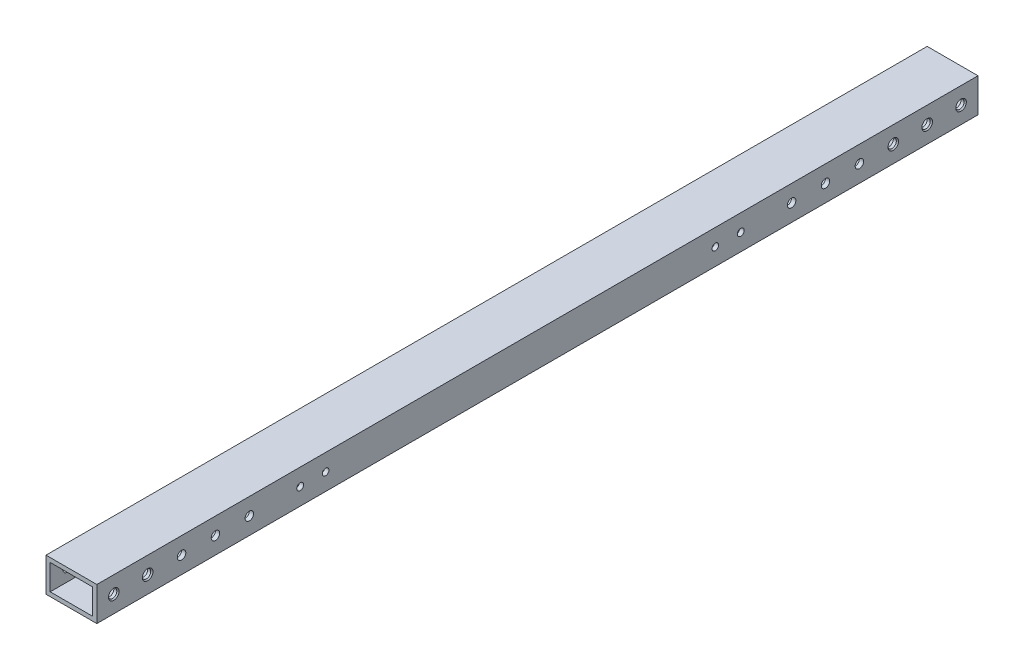
SolidWorks part; units mm, degrees
ref_plane "Front Plane" through (0, 0, 0) normal (0, 0, 1) x (1, 0, 0)
ref_plane "Top Plane" through (0, 0, 0) normal (0, 1, 0) x (1, 0, 0)
ref_plane "Right Plane" through (0, 0, 0) normal (1, 0, 0) x (0, 0, -1)
sketch "Sketch1" plane through (0, 0, 0) normal (0, 0, 1) x (1, 0, 0)
  line L0 (-15.875, 9.525) -> (15.875, 9.525)
  line L2 (-19.05, 12.7) -> (19.05, 12.7)
  line L3 (-19.05, 12.7) -> (-19.05, -12.7)
  line L4 (-19.05, -12.7) -> (19.05, -12.7)
  line L5 (19.05, 12.7) -> (19.05, -12.7)
  line L10 (15.875, 9.525) -> (15.875, -9.525)
  line L11 (-15.875, -9.525) -> (15.875, -9.525)
  line L12 (-15.875, 9.525) -> (-15.875, -9.525)
  point P12 (0, 12.7)
  point P14 (19.05, 0)
  dimension "Wall Thickness" = 3.175
  dimension "Outside Width" = 38.1
  dimension "Outside Height" = 25.4
  dimension "Inside Height" = 19.05
  dimension "Inside Width" = 31.75
sketch "Sketch2" plane through (0, 0, 0) normal (1, 0, 0) x (0, 0, -1)
  line L0 (330.2, 0) -> (-330.2, 0)
  point P4 (0, 0)
  point P7 (-330.2, 0)
  point P10 (330.2, 0)
  dimension "Length" = 660.4
sketch "Sketch3" plane through (0, 0, 0) normal (0, 0, 1) x (1, 0, 0)
  line L21 (19.05, 12.7) -> (-19.05, 12.7)
  line L22 (19.05, -12.7) -> (19.05, 12.7)
  line L23 (-19.05, -12.7) -> (19.05, -12.7)
  line L24 (-19.05, 12.7) -> (-19.05, -12.7)
  line L25 (19.05, 12.7) -> (-19.05, 12.7)
  line L26 (19.05, -12.7) -> (19.05, 12.7)
  line L27 (-19.05, -12.7) -> (19.05, -12.7)
  line L28 (-19.05, 12.7) -> (-19.05, -12.7)
  line L29 (15.875, 9.525) -> (-15.875, 9.525)
  line L30 (15.875, -9.525) -> (15.875, 9.525)
  line L31 (-15.875, -9.525) -> (15.875, -9.525)
  line L32 (-15.875, 9.525) -> (-15.875, -9.525)
  line L33 (15.875, 9.525) -> (-15.875, 9.525)
  line L34 (15.875, -9.525) -> (15.875, 9.525)
  line L35 (-15.875, -9.525) -> (15.875, -9.525)
  line L36 (-15.875, 9.525) -> (-15.875, -9.525)
  dimension "D1" = 0
  dimension "D2" = 0
extrude "Boss-Extrude1" add sketch "Sketch3" along normal up to vertex (330.2 mm away) and the other way up to vertex (330.2 mm away) up to point (0, 0, 330.2) other way up to point (0, 0, -330.2)
sketch "Drawing Reference" plane through (0, 0, 0) normal (1, 0, 0) x (0, 0, -1)
  line L0 (-330.2, 0) -> (330.2, 0) construction
  line L1 (0, -12.7) -> (0, 12.7) construction
  line L2 (-330.2, -12.7) -> (330.2, -12.7) construction
  line L5 (-330.2, 12.7) -> (330.2, 12.7) construction
  point P7 (-302.768, 0)
  point P8 (302.768, 0)
  dimension "D1" = 27.432
sketch "Sketch4" plane through (-19.05, 0, 0) normal (-1, 0, 0) x (0, 0, 1)
  line L0 (-330.2, 0) -> (-317.5, 0)
  line L1 (-330.2, 12.7) -> (-330.2, -12.7) construction
  line L2 (-317.5, 0) -> (-292.1, 0)
  line L3 (-292.1, 0) -> (-266.7, 0)
  line L4 (-266.7, 0) -> (-241.3, 0)
  line L5 (-241.3, 0) -> (-215.9, 0)
  line L6 (-215.9, 0) -> (-190.5, 0)
  line L7 (330.2, 0) -> (317.5, 0)
  line L8 (330.2, 12.7) -> (330.2, -12.7) construction
  line L9 (317.5, 0) -> (292.1, 0)
  line L10 (292.1, 0) -> (266.7, 0)
  line L11 (266.7, 0) -> (241.3, 0)
  line L12 (241.3, 0) -> (215.9, 0)
  line L13 (-190.5, 0) -> (-133.35, 0)
  line L14 (-190.5, 0) -> (-152.4, 0) construction
  line L15 (215.9, 0) -> (158.75, 0)
hole_wizard "1/4 (0.25) Diameter Hole2" positions "Sketch7" profile "Sketch8" hole size "1/4" standard "ANSI Inch" end condition through all
sketch "Sketch7" plane through (-19.05, 0, 0) normal (-1, 0, 0) x (0, 0, 1)
  point P0 (-317.5, 0)
  point P3 (-292.1, 0)
  point P7 (317.5, 0)
  point P11 (-266.7, 0)
  point P14 (292.1, 0)
sketch "Sketch8" plane through (-19.05, 0, -317.5) normal (0, 1, 0) x (0, 0, 1)
  line L0 (0, 0) -> (0, 38.1)
  line L1 (0, 38.1) -> (3.9624, 38.1)
  line L2 (3.175, 37.1942) -> (3.175, 0)
  line L5 (3.175, 0) -> (0, 0)
  line L7 (3.9624, 38.1) -> (3.175, 37.1942)
  line L8 (-3.9624, 38.1) -> (-3.175, 37.1942) construction
  line L11 (0, -6.35) -> (0, 107.95) construction
  dimension "Thru Hole Dia." = 6.35
  dimension "Thru Hole Depth" = 38.1
  dimension "Far C'Sink Dia." = 7.9248
  dimension "Far C'Sink Angle" = 82
hole_wizard "1/4 (0.25) Diameter Hole3" positions "Sketch9" profile "Sketch10" hole size "1/4" standard "ANSI Inch" end condition through all
sketch "Sketch9" plane through (19.05, 0, 0) normal (1, 0, 0) x (0, 0, -1)
  point P0 (-266.7, 0)
  point P3 (-241.3, 0)
  point P6 (-215.9, 0)
  point P9 (241.3, 0)
  point P12 (215.9, 0)
  point P15 (190.5, 0)
sketch "Sketch10" plane through (19.05, 0, 266.7) normal (0, 1, 0) x (0, 0, -1)
  line L0 (0, 0) -> (0, 38.1)
  line L1 (0, 38.1) -> (3.175, 38.1)
  line L2 (3.175, 38.1) -> (3.175, 0)
  line L5 (3.175, 0) -> (0, 0)
  line L11 (0, -6.35) -> (0, 107.95) construction
  dimension "Thru Hole Dia." = 6.35
  dimension "Thru Hole Depth" = 38.1
hole_wizard "13/64 (0.20313) Diameter Hole1" positions "Sketch11" profile "Sketch12" hole size "13/64" standard "ANSI Inch" end condition through all
sketch "Sketch11" plane through (19.05, 0, 0) normal (1, 0, 0) x (0, 0, -1)
  point P0 (152.4, 0)
  point P7 (-177.8, 0)
sketch "Sketch12" plane through (19.05, 0, -152.4) normal (0, 1, 0) x (0, 0, -1)
  line L0 (0, 0) -> (0, 38.1)
  line L1 (0, 38.1) -> (2.5798, 38.1)
  line L2 (2.5798, 38.1) -> (2.5798, 0)
  line L5 (2.5798, 0) -> (0, 0)
  line L11 (0, -6.35) -> (0, 107.95) construction
  dimension "Thru Hole Dia." = 5.1595
  dimension "Thru Hole Depth" = 38.1
hole_wizard "#10 Clearance Hole1" positions "Sketch13" profile "Sketch14" hole size "#10" standard "ANSI Inch" end condition through all
sketch "Sketch13" plane through (-19.05, 0, 0) normal (-1, 0, 0) x (0, 0, 1)
  point P0 (-133.35, 0)
  point P3 (158.75, 0)
sketch "Sketch14" plane through (-19.05, 0, -133.35) normal (0, 1, 0) x (0, 0, 1)
  line L0 (0, 0) -> (0, 38.1)
  line L1 (0, 38.1) -> (2.4892, 38.1)
  line L2 (2.4892, 38.1) -> (2.4892, 0)
  line L5 (2.4892, 0) -> (0, 0)
  line L11 (0, -6.35) -> (0, 107.95) construction
  dimension "Thru Hole Dia." = 4.9784
  dimension "Thru Hole Depth" = 38.1
equation "\"D1@Drawing Reference\"=\"Outside Width@Sketch1\" * 0.72"
